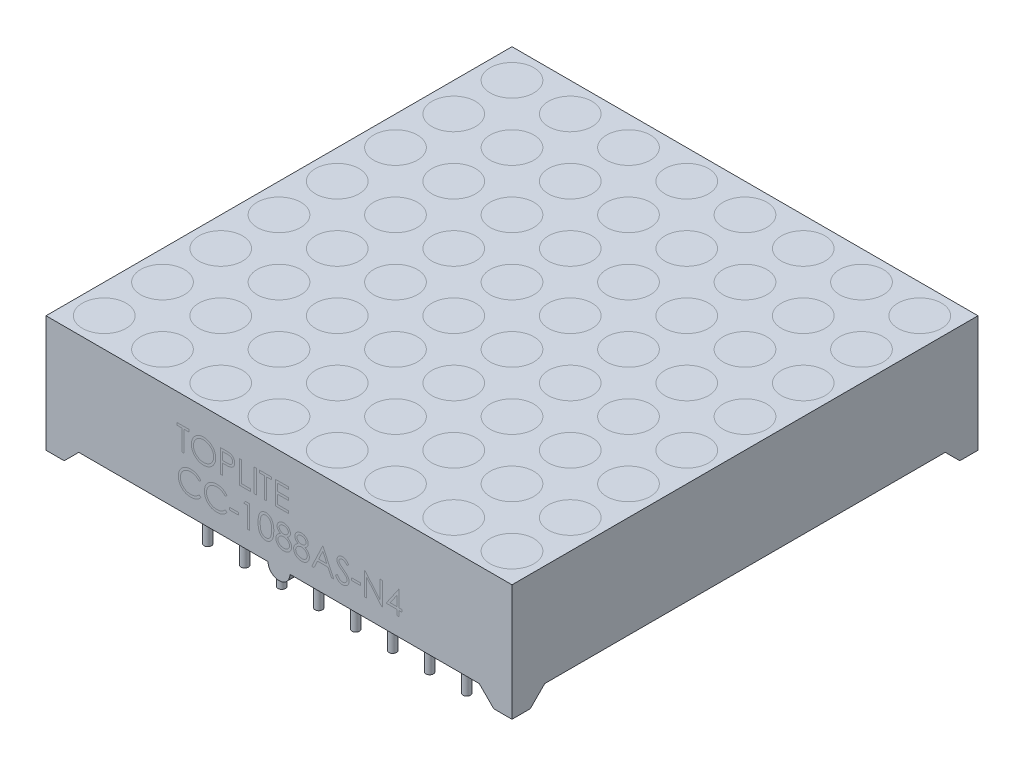
SolidWorks part; units mm, degrees
ref_plane "Front Plane" through (0, 0, 0) normal (0, 0, 1) x (1, 0, 0)
ref_plane "Top Plane" through (0, 0, 0) normal (0, 1, 0) x (1, 0, 0)
ref_plane "Right Plane" through (0, 0, 0) normal (1, 0, 0) x (0, 0, -1)
sketch "Sketch1" plane through (0, 0, 0) normal (0, 1, 0) x (1, 0, 0)
  line L1 (-16, 16) -> (16, 16)
  line L2 (-16, 16) -> (-16, -16)
  line L3 (-16, -16) -> (16, -16)
  line L4 (16, 16) -> (16, -16)
  line L5 (-16, 16) -> (16, -16) construction
  line L6 (-16, -16) -> (16, 16) construction
  point P0 (0, 0)
  dimension "D1" = 32
  dimension "D2" = 32
extrude "Boss-Extrude1" add sketch "Sketch1" along normal blind 8
sketch "Sketch2" plane through (0, 0, 16) normal (0, 0, 1) x (1, 0, 0)
  line L0 (-14.75, 0) -> (-13.75, 1)
  line L1 (-16, 0) -> (16, 0) construction
  line L2 (-13.75, 1) -> (13.75, 1)
  line L3 (13.75, 1) -> (14.75, 0)
  line L4 (-14.75, 0) -> (14.75, 0)
  line L5 (-16, 8) -> (-16, 0) construction
  line L6 (16, 8) -> (16, 0) construction
  dimension "D1" = 1.25
  dimension "D2" = 1.25
  dimension "D3" = 2.25
  dimension "D4" = 2.25
  dimension "D5" = 1
extrude "Cut-Extrude1" cut sketch "Sketch2" against normal up to surface (32 mm away) up to face at (0, 4, -16)
sketch "Sketch3" plane through (16, 0, 0) normal (1, 0, 0) x (0, 0, -1)
  line L0 (-14.75, 0) -> (-13.75, 1)
  line L1 (-16, 0) -> (16, 0) construction
  line L2 (-13.75, 1) -> (13.75, 1)
  line L3 (13.75, 1) -> (14.75, 0)
  line L4 (14.75, 0) -> (-14.75, 0)
  line L5 (-16, 8) -> (-16, 0) construction
  line L6 (16, 8) -> (16, 0) construction
  dimension "D1" = 1.25
  dimension "D2" = 2.25
  dimension "D3" = 1.25
  dimension "D4" = 2.25
  dimension "D5" = 1
extrude "Cut-Extrude2" cut sketch "Sketch3" against normal up to surface (32 mm away) up to face at (-16, 4, 0)
sketch "Sketch4" plane through (0, 1, 0) normal (0, -1, 0) x (1, 0, 0)
  line L0 (13.75, 16) -> (-13.75, 16) construction
  line L1 (-15.5, -15.5) -> (15.5, -15.5)
  line L2 (-15.5, -15.5) -> (-15.5, 15.5)
  line L3 (-15.5, 15.5) -> (15.5, 15.5)
  line L4 (15.5, -15.5) -> (15.5, 15.5)
  line L5 (-15.5, -15.5) -> (15.5, 15.5) construction
  line L6 (-15.5, 15.5) -> (15.5, -15.5) construction
  line L8 (-16, 13.75) -> (-16, -13.75) construction
  point P0 (0, 0)
  dimension "D1" = 0.5
  dimension "D2" = 0.5
extrude "Cut-Extrude4" cut sketch "Sketch4" along normal up to surface (1 mm away) up to face at (-15.375, 0, -15.375)
shell "Shell1" thickness 0.5 removed face at (0, 1, 0)
sketch "Sketch5" plane through (0, 7.5, 0) normal (0, -1, 0) x (1, 0, 0)
  line L4 (15.5, -15.5) -> (15.5, 15.5)
  line L5 (15.5, 15.5) -> (-15.5, 15.5)
  line L6 (-15.5, 15.5) -> (-15.5, -15.5)
  line L7 (-15.5, -15.5) -> (15.5, -15.5)
  line L8 (15.5, -15.5) -> (15.5, 15.5)
  line L9 (15.5, 15.5) -> (-15.5, 15.5)
  line L10 (-15.5, 15.5) -> (-15.5, -15.5)
  line L11 (-15.5, -15.5) -> (15.5, -15.5)
  dimension "D1" = 0
extrude "Boss-Extrude2" add sketch "Sketch5" along normal blind 4 contours L8 L9 L10 L11
sketch "Sketch7" plane through (0, 8, 0) normal (0, 1, 0) x (1, 0, 0)
  line L0 (0, 18.8545) -> (0, -20.0158) construction
  line L1 (-30.1761, 0) -> (31.2444, 0) construction
  line L2 (0, 22.8545) -> (0, -16.0158) construction
  line L3 (0, 26.8545) -> (0, -12.0158) construction
  line L4 (0, 30.8545) -> (0, -8.0158) construction
  circle A0 centre (-14, 2) radius 1.5
  circle A1 centre (-10, 2) radius 1.5
  circle A2 centre (-6, 2) radius 1.5
  circle A3 centre (-2, 2) radius 1.5
  circle A4 centre (2, 2) radius 1.5
  circle A5 centre (6, 2) radius 1.5
  circle A6 centre (10, 2) radius 1.5
  circle A7 centre (14, 2) radius 1.5
  circle A8 centre (14, -2) radius 1.5
  circle A9 centre (10, -2) radius 1.5
  circle A10 centre (6, -2) radius 1.5
  circle A11 centre (2, -2) radius 1.5
  circle A12 centre (-2, -2) radius 1.5
  circle A13 centre (-6, -2) radius 1.5
  circle A14 centre (-10, -2) radius 1.5
  circle A15 centre (-14, -2) radius 1.5
  circle A16 centre (14, -6) radius 1.5
  circle A17 centre (10, -6) radius 1.5
  circle A18 centre (6, -6) radius 1.5
  circle A19 centre (2, -6) radius 1.5
  circle A20 centre (-2, -6) radius 1.5
  circle A21 centre (-6, -6) radius 1.5
  circle A22 centre (-10, -6) radius 1.5
  circle A23 centre (-14, -6) radius 1.5
  circle A24 centre (14, -10) radius 1.5
  circle A25 centre (10, -10) radius 1.5
  circle A26 centre (6, -10) radius 1.5
  circle A27 centre (2, -10) radius 1.5
  circle A28 centre (-2, -10) radius 1.5
  circle A29 centre (-6, -10) radius 1.5
  circle A30 centre (-10, -10) radius 1.5
  circle A31 centre (-14, -10) radius 1.5
  circle A32 centre (14, -14) radius 1.5
  circle A33 centre (10, -14) radius 1.5
  circle A34 centre (6, -14) radius 1.5
  circle A35 centre (2, -14) radius 1.5
  circle A36 centre (-2, -14) radius 1.5
  circle A37 centre (-6, -14) radius 1.5
  circle A38 centre (-10, -14) radius 1.5
  circle A39 centre (-14, -14) radius 1.5
  circle A40 centre (-14, 6) radius 1.5
  circle A41 centre (-10, 6) radius 1.5
  circle A42 centre (-6, 6) radius 1.5
  circle A43 centre (-2, 6) radius 1.5
  circle A44 centre (2, 6) radius 1.5
  circle A45 centre (6, 6) radius 1.5
  circle A46 centre (10, 6) radius 1.5
  circle A47 centre (14, 6) radius 1.5
  circle A48 centre (-14, 10) radius 1.5
  circle A49 centre (-10, 10) radius 1.5
  circle A50 centre (-6, 10) radius 1.5
  circle A51 centre (-2, 10) radius 1.5
  circle A52 centre (2, 10) radius 1.5
  circle A53 centre (6, 10) radius 1.5
  circle A54 centre (10, 10) radius 1.5
  circle A55 centre (14, 10) radius 1.5
  circle A56 centre (-14, 14) radius 1.5
  circle A57 centre (-10, 14) radius 1.5
  circle A58 centre (-6, 14) radius 1.5
  circle A59 centre (-2, 14) radius 1.5
  circle A60 centre (2, 14) radius 1.5
  circle A61 centre (6, 14) radius 1.5
  circle A62 centre (10, 14) radius 1.5
  circle A63 centre (14, 14) radius 1.5
  dimension "D1" = 3
  dimension "D2" = 4
  dimension "D3" = 4
  dimension "D4" = 4
  dimension "D5" = 4
  dimension "D6" = 4
  dimension "D7" = 4
  dimension "D8" = 4
  dimension "D9" = 4
  dimension "D10" = 4
  dimension "D11" = 4
wrap "Wrap1" sketch "Sketch7" wrap type scribe source sketch "Sketch7" face at (0, 8, 0)
sketch "Sketch6" plane through (0, 3.5, 0) normal (0, -1, 0) x (1, 0, 0)
  line L0 (-18.2598, 0) -> (16.9858, 0) construction
  line L1 (0, 12.8809) -> (0, -14.202) construction
  line L2 (-8.89, 12) -> (8.89, 12) construction
  circle A0 centre (-8.89, 12) radius 0.255
  circle A1 centre (-6.35, 12) radius 0.255
  circle A2 centre (-3.81, 12) radius 0.255
  circle A3 centre (-1.27, 12) radius 0.255
  circle A4 centre (1.27, 12) radius 0.255
  circle A5 centre (3.81, 12) radius 0.255
  circle A6 centre (6.35, 12) radius 0.255
  circle A7 centre (8.89, 12) radius 0.255
  circle A8 centre (8.89, -12) radius 0.255
  circle A9 centre (6.35, -12) radius 0.255
  circle A10 centre (3.81, -12) radius 0.255
  circle A11 centre (1.27, -12) radius 0.255
  circle A12 centre (-1.27, -12) radius 0.255
  circle A13 centre (-3.81, -12) radius 0.255
  circle A14 centre (-6.35, -12) radius 0.255
  circle A15 centre (-8.89, -12) radius 0.255
  point P21 (0, 0)
  point P22 (0.7096, 12.3727)
  point P23 (0, 0)
  point P24 (0, 0)
  point P25 (0, 0)
  point P26 (0, 0)
  point P27 (0, 0)
  point P28 (0, 0)
  point P29 (0, 0)
  point P30 (0, 0)
  point P31 (0, 0)
  dimension "D1" = 0.51
  dimension "D2" = 2.54
  dimension "D3" = 2.54
  dimension "D4" = 2.54
  dimension "D5" = 2.54
  dimension "D6" = 2.54
  dimension "D7" = 2.54
  dimension "D8" = 2.54
  dimension "D9" = 24
extrude "Boss-Extrude3" add sketch "Sketch6" along normal blind 7.5
sketch "Sketch8" plane through (0, 0, 16) normal (0, 0, 1) x (1, 0, 0)
  line L0 (-7.0332, 4.5642) -> (12.9308, 4.5642) construction
  line L1 (-7.0332, 2.2198) -> (13.5535, 2.2198) construction
  text T0 "TOPLITE" font "Century Gothic" height in points 6
  text T1 "CC-1088AS-N4" font "Century Gothic" height in points 6
  point P6 (13.5535, 1.707)
  point P7 (12.9308, 4.6374)
  point P8 (-8.1321, 2.2198)
  point P9 (-7.0332, 2.2198)
  point P10 (-7.0332, 4.5642)
wrap "Wrap2" sketch "Sketch8" wrap type scribe source sketch "Sketch8" face at (0, 2.25, 16)
sketch "Sketch9" plane through (0, 0, 16) normal (0, 0, 1) x (1, 0, 0)
  line L0 (13.75, 1) -> (-13.75, 1) construction
  line L1 (-0.75, 1) -> (0.75, 1)
  arc A0 (-0.75, 1) -> (0.75, 1) centre (0, 1) ccw
  dimension "D1" = 1.5
extrude "Boss-Extrude4" add sketch "Sketch9" against normal up to surface (0.5 mm away) up to face at (0, 1.125, 15.5)
